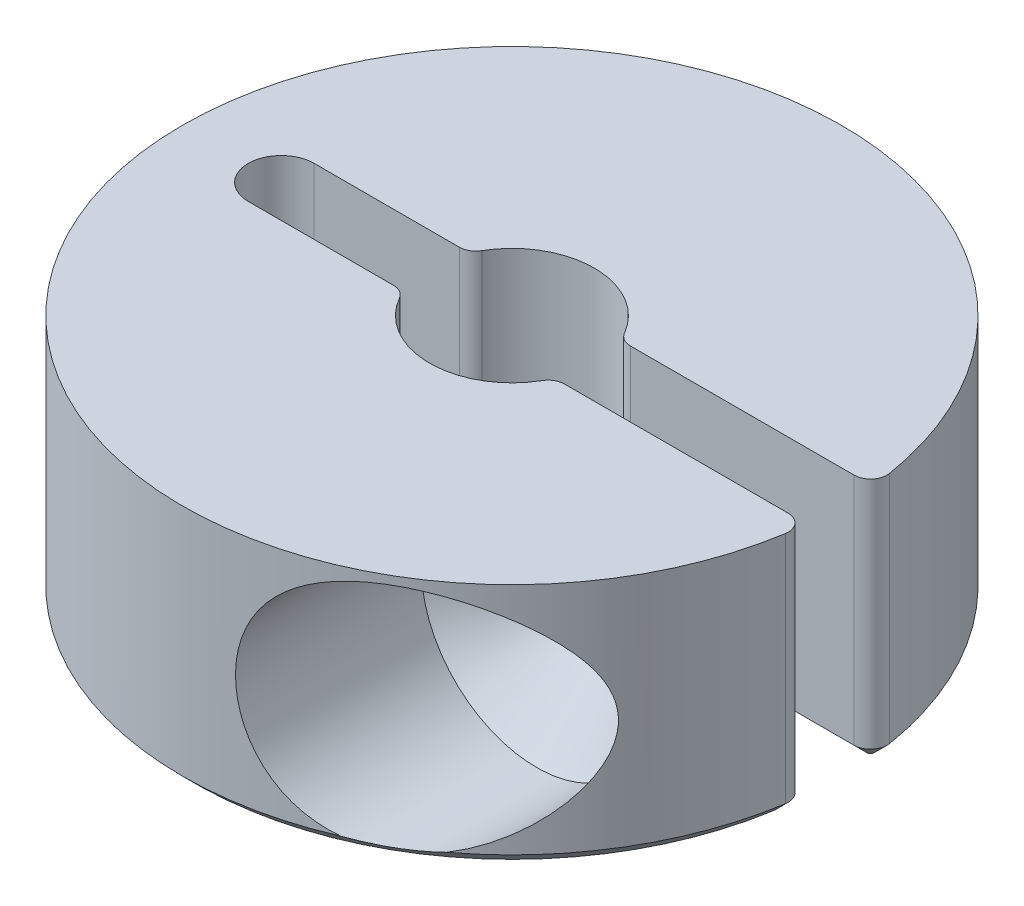
SolidWorks part; units mm, degrees
ref_plane "Front Plane" through (0, 0, 0) normal (0, 0, 1) x (1, 0, 0)
ref_plane "Top Plane" through (0, 0, 0) normal (0, 1, 0) x (1, 0, 0)
ref_plane "Right Plane" through (0, 0, 0) normal (1, 0, 0) x (0, 0, -1)
sketch "Sketch1" plane through (0, 0, 0) normal (0, 1, 0) x (1, 0, 0)
  circle A0 centre (0, 0) radius 10
  circle A1 centre (0, 0) radius 2.5
  dimension "D1" = 20
  dimension "D2" = 5
extrude "Boss-Extrude1" add sketch "Sketch1" along normal mid plane 7.5
sketch "Sketch2" plane through (0, 3.75, 0) normal (0, 1, 0) x (1, 0, 0)
  line L0 (10, 0) -> (-7, 0) construction
  line L1 (10, -1) -> (-7, -1)
  line L2 (10, 1) -> (-7, 1)
  circle A0 centre (0, 0) radius 10 construction
  arc A1 (10, -1) -> (10, 1) centre (10, 0) ccw
  arc A2 (-7, 1) -> (-7, -1) centre (-7, 0) ccw
  point P4 (1.5, 0)
  dimension "D1" = 1
  dimension "D2" = 7
extrude "Cut-Extrude1" cut sketch "Sketch2" against normal through all
sketch "Sketch3" plane through (0, 0, -1) normal (0, 0, 1) x (1, 0, 0)
  circle A0 centre (5, 0) radius 1.25
  dimension "D1" = 2.5
  dimension "D2" = 5
extrude "Cut-Extrude2" cut sketch "Sketch3" against normal through all and the other way through all
sketch "Sketch4" plane through (0, 0, -1) normal (0, 0, 1) x (1, 0, 0)
  circle A0 centre (5, 0) radius 1.75
  dimension "D1" = 3.5
extrude "Cut-Extrude3" cut sketch "Sketch4" along normal through all
sketch "Sketch5" plane through (0, 0, -1) normal (0, 0, 1) x (1, 0, 0)
  circle A0 centre (5, 0) radius 3.5
  dimension "D1" = 7
extrude "Cut-Extrude4" cut sketch "Sketch5" along normal blind 8 from offset 6
chamfer "Chamfer1" distance 2.5 angle 45 1 edges at (6.75, 0, 5)
fillet "Fillet1" radius 0.5 6 edges at (9.9499, 0, 1) (2.2913, 0, 1) (-2.2913, 0, 1) (-2.2913, 0, -1) (2.2913, 0, -1) (9.9499, 0, -1)
chamfer "Chamfer2" distance 0.4 angle 45 14 edges at (9.7613, -3.75, 1.1756) (-10, -3.75, 0) (5.9895, -3.75, 1) (9.7613, -3.75, -1.1756) (2.3481, -3.75, 1.067) (5.9895, -3.75, -1) (0, -3.75, 2.5) (2.3481, -3.75, -1.067) (-2.3481, -3.75, 1.067) (0, -3.75, -2.5) (-4.799, -3.75, 1) (-2.3481, -3.75, -1.067) (-8, -3.75, 0) (-4.799, -3.75, -1)
